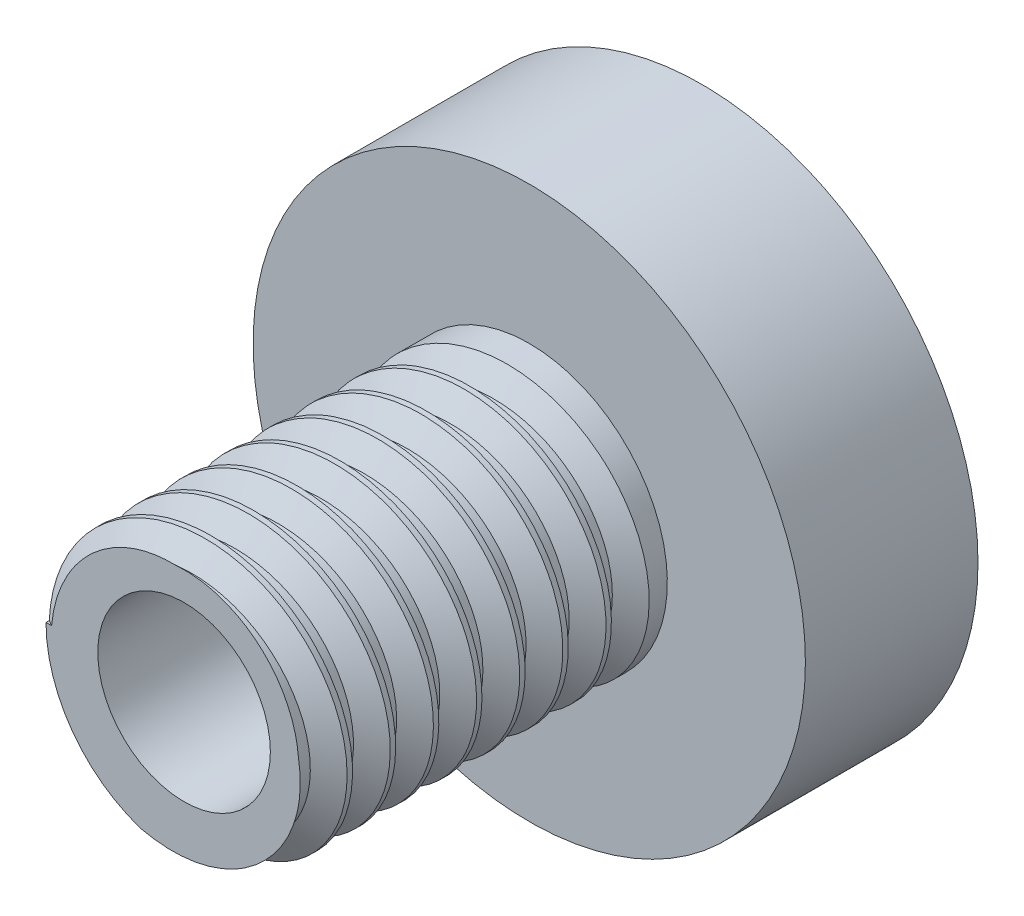
SolidWorks part; units mm, degrees
ref_plane "Front Plane" through (0, 0, 0) normal (0, 0, 1) x (1, 0, 0)
ref_plane "Top Plane" through (0, 0, 0) normal (0, 1, 0) x (1, 0, 0)
ref_plane "Right Plane" through (0, 0, 0) normal (1, 0, 0) x (0, 0, -1)
sketch "Эскиз1" plane through (0, 0, 0) normal (0, 1, 0) x (1, 0, 0)
  line L0 (0, 0) -> (0, 6.8777) construction
  line L1 (-4, 0) -> (-4, 10)
  line L2 (-4, 10) -> (-8, 10)
  line L3 (-8, 10) -> (-8, 15)
  line L4 (-8, 15) -> (-2.5, 15)
  line L5 (-2.5, 15) -> (-2.5, 0)
  line L6 (-2.5, 0) -> (-4, 0)
  line L7 (-2.5, 0) -> (0, 0) construction
  dimension "D1" = 8
  dimension "D2" = 5
  dimension "D3" = 10
  dimension "D4" = 5
  dimension "D5" = 16
revolve "Повернуть1" add sketch "Эскиз1" angle 360 about L0
thread "Резьба1" pitch 1.25 method cut profile "Профиль резьбы1" start angle 0, offset 1, length 10, pitch 1.25, diameter 8
ref_plane "Плоскость1" through (-4, 0, 1) normal (0, -1, 0) x (-1, 0, 0)
sketch "Профиль резьбы1" plane through (-4, 0, 1) normal (0, -1, 0) x (-1, 0, 0)
  line L0 (0, 0) -> (0, 1.25) construction
  line L11 (0, 0) -> (0, 1.0937)
  line L12 (0, 1.0937) -> (-0.6766, 0.7031)
  line L13 (-0.6766, 0.7031) -> (-0.6766, 0.3906)
  line L15 (-0.6766, 0.3906) -> (0, 0)
  line L17 (-0.6766, 0.5469) -> (0, 0.5469) construction
  point P2 (0, 0)
  dimension "Pitch" = 1.25
  dimension "Profile_Angle" = 60
  dimension "Profile_Land" = 0.3125
  dimension "Profile_Height" = 0.6766
